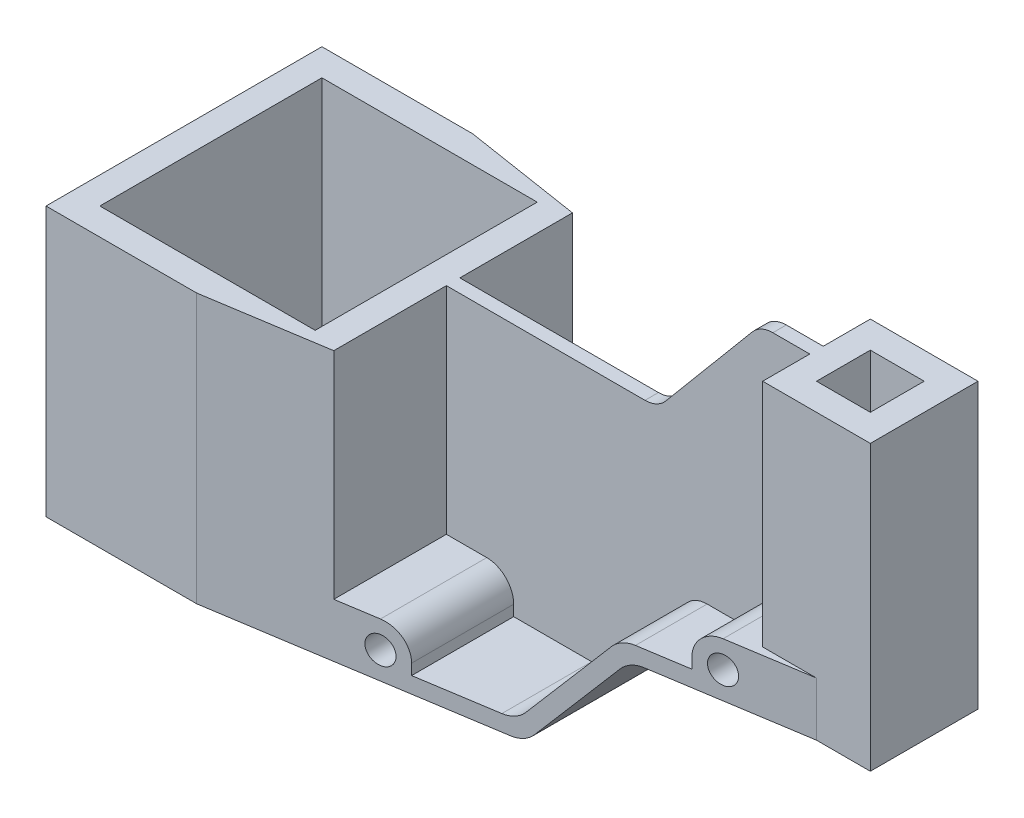
SolidWorks part; units mm, degrees
material "Alliage 1060"
ref_plane "Plan de face" through (0, 0, 0) normal (0, 0, 1) x (1, 0, 0)
ref_plane "Plan de dessus" through (0, 0, 0) normal (0, 1, 0) x (1, 0, 0)
ref_plane "Plan de droite" through (0, 0, 0) normal (1, 0, 0) x (0, 0, -1)
sketch "Esquisse1" plane through (0, 0, 0) normal (0, 0, 1) x (1, 0, 0)
  line L0 (50, 20) -> (65, 20)
  line L2 (0, 0) -> (0, 100)
  line L4 (-50, 0) -> (-50, 100)
  line L6 (0, 0) -> (0, 100)
  line L8 (50, 0) -> (50, 100)
  line L12 (225, 40) -> (225, 145.5)
  line L13 (75, 10) -> (75, 6)
  line L14 (75, 6) -> (103.9751, 6)
  line L15 (111.6355, 9.5721) -> (139.2048, 42.4279)
  line L16 (146.8652, 46) -> (165, 46)
  line L17 (165, 46) -> (165, 50)
  line L18 (175, 60) -> (205, 60)
  line L19 (205, 40) -> (205, 145.5)
  line L20 (149.6631, 40) -> (225, 40)
  line L21 (114.4334, 3.5721) -> (142.0026, 36.4279)
  line L22 (-50, 100) -> (123.7808, 100)
  line L23 (131.4412, 103.5721) -> (163.6255, 141.9279)
  line L24 (171.286, 145.5) -> (225, 145.5)
  line L25 (-50, 0) -> (96.6819, 0)
  line L26 (185, 60) -> (185, 145.5)
  line L27 (0, 100) -> (0, 145.5)
  line L28 (0, 145.5) -> (171.286, 145.5)
  line L29 (96.6819, 0) -> (225, 0)
  line L30 (225, 0) -> (225, 40)
  circle A0 centre (65, 10) radius 5
  circle A1 centre (175, 50) radius 5
  arc A2 (165, 50) -> (175, 60) centre (175, 50) cw
  arc A3 (65, 20) -> (75, 10) centre (65, 10) cw
  arc A6 (139.2048, 42.4279) -> (146.8652, 46) centre (146.8652, 36) cw
  arc A7 (103.9751, 6) -> (111.6355, 9.5721) centre (103.9751, 16) ccw
  arc A9 (163.6255, 141.9279) -> (171.286, 145.5) centre (171.286, 135.5) cw
  arc A10 (123.7808, 100) -> (131.4412, 103.5721) centre (123.7808, 110) ccw
  arc A11 (106.7729, 0) -> (114.4334, 3.5721) centre (106.7729, 10) ccw
  arc A12 (142.0026, 36.4279) -> (149.6631, 40) centre (149.6631, 30) cw
  point P48 (145, 40)
  dimension "D14" = 10
  dimension "D15" = 10
  dimension "D16" = 10
  dimension "D8" = 10
  dimension "D20" = 10
  dimension "D17" = 10
  dimension "D29" = 10
  dimension "D30" = 10
  dimension "B" = 100
  dimension "D2" = 10
  dimension "Z" = 115
  dimension "D6" = 130
  dimension "D7" = 6
  dimension "D12" = 10
  dimension "D13" = 10
  dimension "D19" = 50
  dimension "A" = 205
  dimension "X" = 51.25
  dimension "Y" = 105.5
  dimension "D21" = 100
  dimension "D22" = 20
  dimension "D3" = 50
  dimension "D4" = 20
  dimension "D11" = 10
  dimension "D23" = 6
  dimension "D24" = 6
  dimension "D25" = 40
  dimension "D27" = 20
  dimension "D28" = 60
  dimension "D26" = 40
extrude "Boss.-Extru.1" add sketch "Esquisse1" along normal mid plane 102.5 contours L4 L25 L2 L22 region at (-25, 50, 0)
sketch "Esquisse2" plane through (0, 100, 0) normal (0, 1, 0) x (1, 0, 0)
  line L0 (0, 51.25) -> (6, 51.25)
  line L1 (6, 51.25) -> (205, 20)
  line L2 (0, -51.25) -> (0, 51.25) construction
  line L3 (185, -20) -> (225, -20)
  line L4 (-56.1426, 0) -> (227.5047, 0) construction
  line L5 (185, -20) -> (185, 20)
  line L6 (185, 20) -> (225, 20)
  line L7 (225, -20) -> (225, 20)
  line L8 (185, -20) -> (225, 20) construction
  line L9 (185, 20) -> (225, -20) construction
  line L10 (195, 10) -> (215, 10)
  line L11 (215, -10) -> (215, 10)
  line L12 (195, -10) -> (215, -10)
  line L13 (195, -10) -> (195, 10)
  line L14 (-40, 41.25) -> (-40, -41.25)
  line L15 (-50, 51.25) -> (6, 51.25)
  line L18 (50, 44.3405) -> (50, -44.3405)
  line L19 (-40, -41.25) -> (40, -41.25)
  line L20 (40, 41.25) -> (40, -41.25)
  line L21 (-40, 41.25) -> (40, 41.25)
  line L22 (-50, -51.25) -> (-50, 51.25) construction
  line L23 (-50, 51.25) -> (50, 51.25) construction
  line L24 (50, 51.25) -> (50, -51.25) construction
  line L25 (-50, -51.25) -> (50, -51.25) construction
  line L26 (-50, 51.25) -> (-50, -51.25) construction
  line L27 (6, -51.25) -> (205, -20)
  line L28 (0, -51.25) -> (6, -51.25)
  line L29 (0, 51.25) -> (0, 41.25)
  line L30 (0, -41.25) -> (0, -51.25)
  line L31 (-50, -51.25) -> (0, -51.25) construction
  point P5 (205, 0)
  line M20 (0, -51.25) -> (0, 51.25)
  dimension "D8" = 10
  dimension "D1" = 205
  dimension "D2" = 6
  dimension "D3" = 40
  dimension "D4" = 40
  dimension "D6" = 10
  dimension "D7" = 10
  dimension "D9" = 10
  dimension "D10" = 100
  dimension "D5" = 10
extrude "Boss.-Extru.2" add sketch "Esquisse2" against normal blind 100 and the other way blind 45.5 contours L18 L27 L3 L5 L6 L1 | L28 L27 L18 L1 L0 L21 L20 L19 M20 | L3 L7 L6 L5 L12 L13 L10 L11 region at (3, 100, -50.1096) region at (110.9877, 100, 0) region at (215, 100, -19.4343)
extrude "Enlèv. mat.-Extru.1" cut sketch "Esquisse2<3>" against normal through all contours L21 L14 L19 M20 | L21 L19 L20 M20 region at (-20, 100, 0) region at (20, 100, 0)
sketch "Esquisse2<3>" plane through (0, 100, 0) normal (0, 1, 0) x (1, 0, 0) same geometry as "Esquisse2"
extrude "Enlèv. mat.-Extru.3" cut sketch "Esquisse1<4>" against normal through all from offset 2.5 contours A9 L23 A10 L22 L8 L0 A3 L13 L14 A7 L15 A6 L16 L17 A2 L18 L26 L24 region at (117.1167, 70.0222, 0) offset against normal yes
sketch "Esquisse1<4>" plane through (0, 0, 0) normal (0, 0, 1) x (1, 0, 0) same geometry as "Esquisse1"
extrude "Enlèv. mat.-Extru.4" cut sketch "Esquisse1<5>" along normal through all from offset 2.5 contours A9 L23 A10 L22 L8 L0 A3 L13 L14 A7 L15 A6 L16 L17 A2 L18 L26 L24 region at (117.1167, 70.0222, 0)
sketch "Esquisse1<5>" plane through (0, 0, 0) normal (0, 0, 1) x (1, 0, 0) same geometry as "Esquisse1"
extrude "Enlèv. mat.-Extru.5" cut sketch "Esquisse1<6>" against normal through all both and the other way through all contours L23 A9 L28 L27 L22 A10 | L21 L29 L30 L20 | A0 | A1 region at (74.1957, 123.7509, 0) region at (176.0975, 18.8142, 0)
sketch "Esquisse1<6>" plane through (0, 0, 0) normal (0, 0, 1) x (1, 0, 0) same geometry as "Esquisse1"
extrude "Enlèv. mat.-Extru.6" cut sketch "Esquisse1<7>" against normal blind 31.25 from offset 20 contours L26 L18 L19 L24 region at (195, 102.75, 0) offset against normal yes
sketch "Esquisse1<7>" plane through (0, 0, 0) normal (0, 0, 1) x (1, 0, 0) same geometry as "Esquisse1"
extrude "Enlèv. mat.-Extru.7" cut sketch "Esquisse1<8>" along normal blind 31.25 from offset 20 contours L26 L18 L19 L24 region at (195, 102.75, 0)
sketch "Esquisse1<8>" plane through (0, 0, 0) normal (0, 0, 1) x (1, 0, 0) same geometry as "Esquisse1"
equation "\"D3@Esquisse1\"=\"B@Esquisse1\"/2"
equation "\"Z@Esquisse1\" = \"B@Esquisse1\" + 15"
equation "\"D21@Esquisse1\"=\"B@Esquisse1\""
equation "\"Y@Esquisse1\" = \"B@Esquisse1\" + 5.5"
equation "\"X@Esquisse1\" = \"A@Esquisse1\" / 4"
equation "\"D10@Esquisse2\"=\"B@Esquisse1\""
equation "\"D1@Esquisse2\"=\"A@Esquisse1\""
equation "\"D1@Boss.-Extru.1\"=\"A@Esquisse1\"/2"
equation "\"D1@Boss.-Extru.2\"=\"D10@Esquisse2\""
equation "\"D1@Enlèv. mat.-Extru.6\"=(\"A@Esquisse1\"/2-\"D26@Esquisse1\")/2"
equation "\"D1@Enlèv. mat.-Extru.7\"=(\"A@Esquisse1\"/2-\"D26@Esquisse1\")/2"
equation "\"A\" = 205"
equation "\"B\"= 100"
